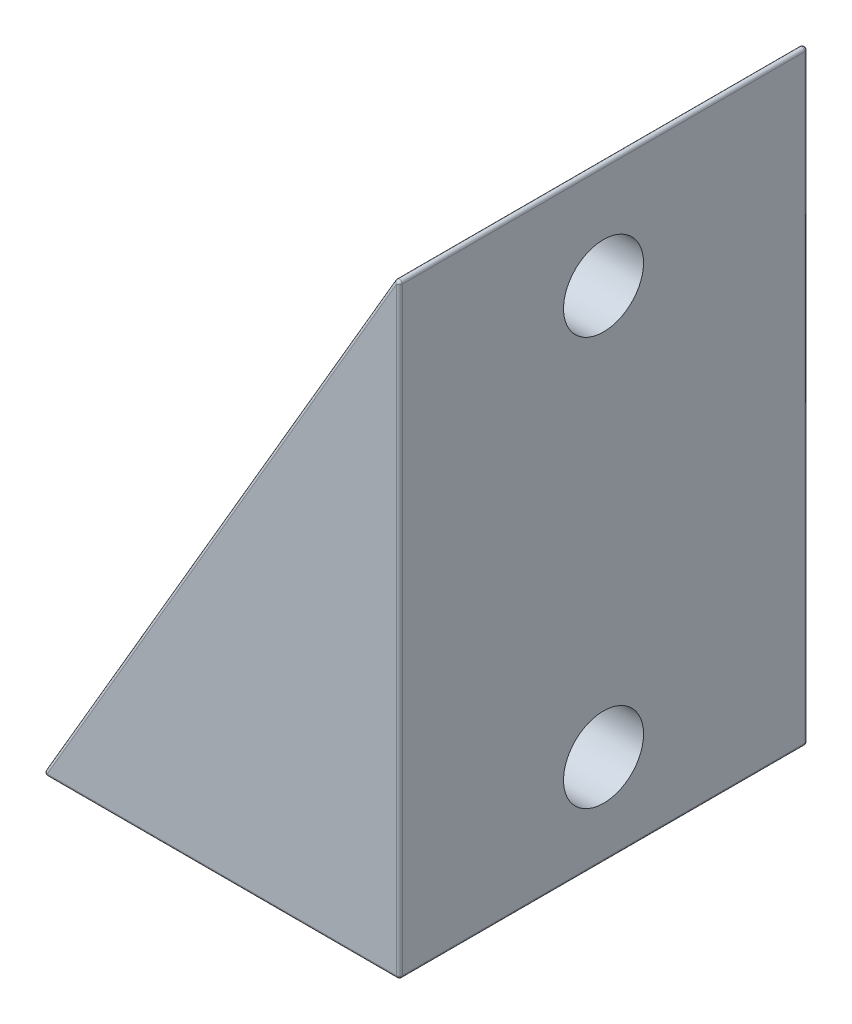
SolidWorks part; units mm, degrees
material "PET"
ref_plane "Front Plane" through (0, 0, 0) normal (0, 0, 1) x (1, 0, 0)
ref_plane "Top Plane" through (0, 0, 0) normal (0, 1, 0) x (1, 0, 0)
ref_plane "Right Plane" through (0, 0, 0) normal (1, 0, 0) x (0, 0, -1)
sketch "Sketch1" plane through (0, 0, 0) normal (0, 0, 1) x (1, 0, 0)
  line L0 (0, 0) -> (0, 38.1)
  line L1 (0, 38.1) -> (-22.225, 0)
  line L2 (-22.225, 0) -> (0, 0)
  dimension "D1" = 38.1
  dimension "D2" = 22.225
extrude "Boss-Extrude1" add sketch "Sketch1" along normal blind 25.4
fillet "Fillet1" radius 0.1778 9 edges at (-11.1125, 0, 0) (0, 19.05, 0) (-11.1125, 19.05, 0) (-11.1125, 0, 25.4) (-11.1125, 19.05, 25.4) (-22.225, 0, 12.7) (0, 38.1, 12.7) (0, 0, 12.7) (0, 19.05, 25.4)
sketch "Sketch2" plane through (0, 0, 0) normal (1, 0, 0) x (0, 0, -1)
  line L0 (-0.1778, 37.4423) -> (-25.2222, 37.4423) construction
  circle A0 centre (-12.7, 31.0923) radius 2.4892
  circle A1 centre (-12.7, 5.6923) radius 2.4892
  point P6 (-12.7, 37.4423)
  dimension "D1" = 4.9784
  dimension "D2" = 6.35
  dimension "D3" = 25.4
extrude "Cut-Extrude1" cut sketch "Sketch2" against normal blind 50.8
